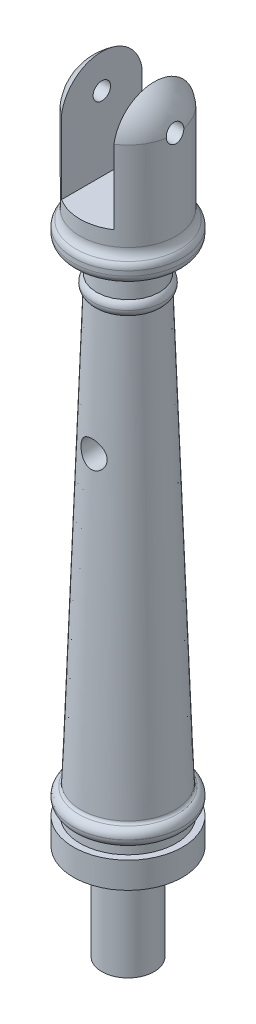
SolidWorks part; units mm, degrees
ref_plane "Front Plane" through (0, 0, 0) normal (0, 0, 1) x (1, 0, 0)
ref_plane "Top Plane" through (0, 0, 0) normal (0, 1, 0) x (1, 0, 0)
ref_plane "Right Plane" through (0, 0, 0) normal (1, 0, 0) x (0, 0, -1)
sketch "Sketch2" plane through (0, 0, 0) normal (0, 0, 1) x (1, 0, 0)
  line L0 (0, 0) -> (0, 114)
  line L1 (0, 114) -> (7, 114)
  line L2 (7, 114) -> (11, 0)
  line L3 (11, 0) -> (0, 0)
  dimension "D1" = 114
  dimension "D2" = 7
  dimension "D3" = 11
revolve "Revolve1" add sketch "Sketch2" angle 360 about L0
sketch "Sketch3" plane through (0, 0, 0) normal (0, -1, 0) x (1, 0, 0)
  circle A0 centre (0, 0) radius 12.5
  dimension "D1" = 25
extrude "Boss-Extrude1" add sketch "Sketch3" along normal blind 6
sketch "Sketch5" plane through (0, -6, 0) normal (0, -1, 0) x (1, 0, 0)
  circle A1 centre (0, 0) radius 12.5
  circle A2 centre (0, 0) radius 12.5
  dimension "D1" = 0
extrude "Boss-Extrude3" add sketch "Sketch5" along normal blind 4 from offset 12 offset against normal yes
fillet "Fillet1" radius 2 2 edges at (0, 6, -12.5) (0, 2, -12.5)
sketch "Sketch6" plane through (0, -6, 0) normal (0, -1, 0) x (1, 0, 0)
  circle A0 centre (0, 0) radius 6
  dimension "D1" = 12
extrude "Boss-Extrude4" add sketch "Sketch6" along normal blind 22
sketch "Sketch7" plane through (0, -28, 0) normal (0, -1, 0) x (1, 0, 0)
  line L0 (-5, 3.3166) -> (-5, -3.3166)
  circle A0 centre (0, 0) radius 6 construction
  arc A1 (-5, 3.3166) -> (-5, -3.3166) centre (0, 0) ccw
  dimension "D1" = 5
extrude "Cut-Extrude1" cut sketch "Sketch7" against normal blind 15
sketch "Sketch8" plane through (0, 114, 0) normal (0, 1, 0) x (1, 0, 0)
  circle A0 centre (0, 0) radius 8
  dimension "D1" = 16
extrude "Boss-Extrude5" add sketch "Sketch8" along normal mid plane 4 from offset 8 separate body offset against normal yes
fillet "Fillet2" radius 2 2 edges at (0, 104, 8) (0, 108, 8)
sketch "Sketch9" plane through (0, 114, 0) normal (0, 1, 0) x (1, 0, 0)
  circle A0 centre (0, 0) radius 12.5
  dimension "D1" = 25
extrude "Boss-Extrude6" add sketch "Sketch9" along normal blind 5
sketch "Sketch10" plane through (0, 119, 0) normal (0, 1, 0) x (1, 0, 0)
  circle A0 centre (0, 0) radius 11
  dimension "D1" = 22
extrude "Boss-Extrude7" add sketch "Sketch10" along normal blind 22
fillet "Fillet3" radius 2 2 edges at (0, 114, 12.5) (0, 119, 12.5)
fillet "Fillet4" radius 3 1 edges at (0, 119, 11)
fillet "Fillet5" radius 0.75 1 edges at (0, 6, -10.7895)
sketch "Sketch11" plane through (0, 0, 0) normal (0, 0, 1) x (1, 0, 0)
  line L0 (11, 141) -> (0, 141)
  line L1 (11, 141) -> (-11, 141) construction
  line L2 (0, 141) -> (0, 150.5)
  line L3 (11, 120.6342) -> (11, 141) construction
  arc A0 (0, 150.5) -> (11, 141) centre (0.1027, 139.5005) cw
  point P4 (0, 0)
  point P8 (0, 0)
  dimension "D2" = 11
  dimension "D1" = 9.5
revolve "Revolve2" add sketch "Sketch11" angle 360 about L2
sketch "Sketch12" plane through (0, 0, 0) normal (0, 0, 1) x (1, 0, 0)
  line L0 (0, 178.9713) -> (0, -90.7714) construction
  line L1 (6, 124) -> (-6, 124)
  line L2 (6, 124) -> (6, 152)
  line L3 (6, 152) -> (-6, 152)
  line L4 (-6, 124) -> (-6, 152)
  line L5 (6, 124) -> (-6, 152) construction
  line L6 (6, 152) -> (-6, 124) construction
  line L7 (11, 141) -> (-11, 141) construction
  point P0 (0, 138)
  dimension "D1" = 12
  dimension "D2" = 17
  dimension "D3" = 28
extrude "Cut-Extrude2" cut sketch "Sketch12" against normal through all both and the other way through all
sketch "Sketch13" plane through (0, 0, 0) normal (0, 0, 1) x (1, 0, 0)
  line L0 (-12.5, -6) -> (12.5, -6) construction
  circle A0 centre (0, 76) radius 3
  point P4 (0, 0)
  dimension "D1" = 82
  dimension "D2" = 6
extrude "Cut-Extrude3" cut sketch "Sketch13" against normal through all both and the other way through all
sketch "Sketch14" plane through (0, 0, 0) normal (1, 0, 0) x (0, 0, -1)
  line L0 (-9.2195, 141) -> (9.2195, 141) construction
  circle A0 centre (0, 141) radius 2
  dimension "D1" = 4
extrude "Cut-Extrude4" cut sketch "Sketch14" against normal through all both and the other way through all
